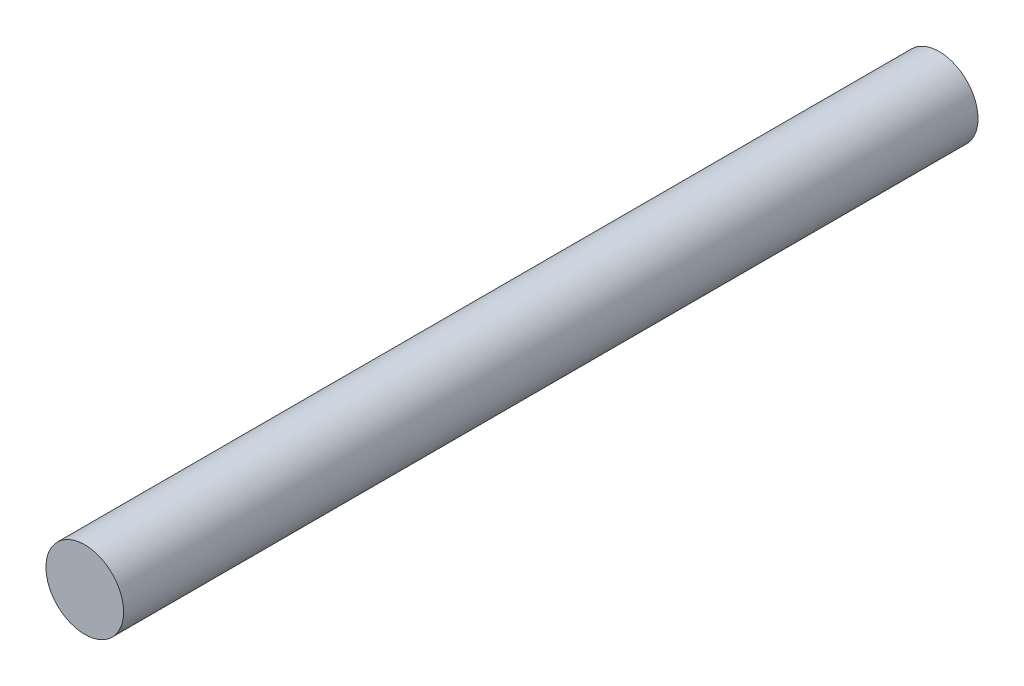
SolidWorks part; units mm, degrees
ref_plane "Front Plane" through (0, 0, 0) normal (0, 0, 1) x (1, 0, 0)
ref_plane "Top Plane" through (0, 0, 0) normal (0, 1, 0) x (1, 0, 0)
ref_plane "Right Plane" through (0, 0, 0) normal (1, 0, 0) x (0, 0, -1)
sketch "Sketch1" plane through (0, 0, 0) normal (0, 0, 1) x (1, 0, 0)
  circle A0 centre (0, 0) radius 1
  dimension "D1" = 2
extrude "Boss-Extrude1" add sketch "Sketch1" along normal blind 11 and the other way blind 11
